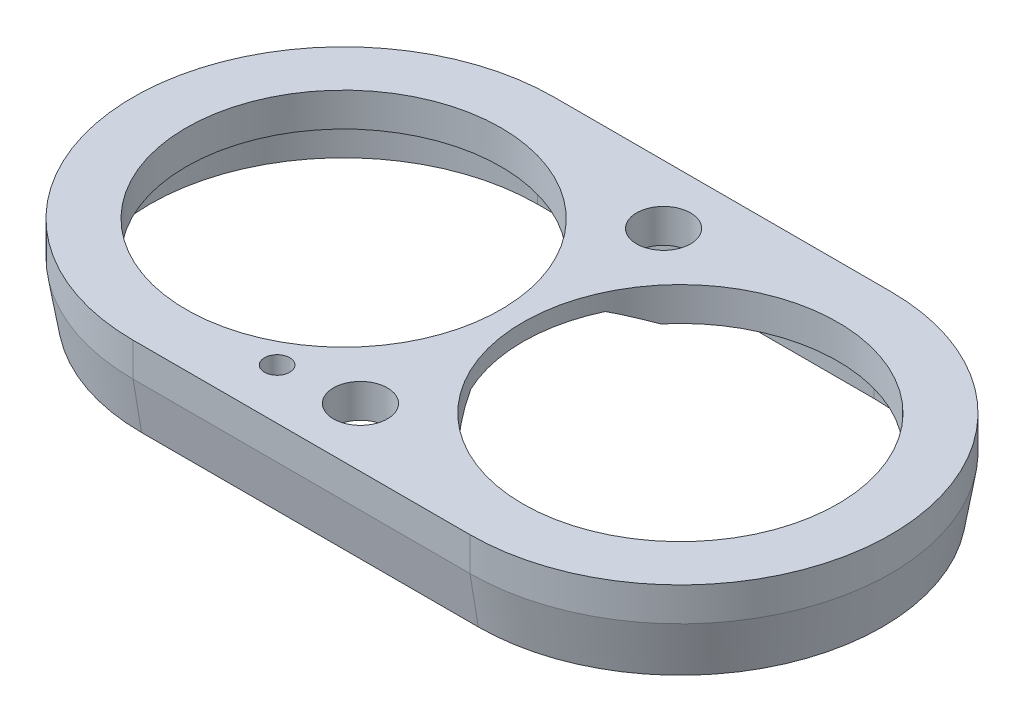
SolidWorks part; units mm, degrees
ref_plane "Front Plane" through (0, 0, 0) normal (0, 0, 1) x (1, 0, 0)
ref_plane "Top Plane" through (0, 0, 0) normal (0, 1, 0) x (1, 0, 0)
ref_plane "Right Plane" through (0, 0, 0) normal (1, 0, 0) x (0, 0, -1)
sketch "Sketch1" plane through (0, 0, 0) normal (0, 1, 0) x (1, 0, 0)
  line L2 (10, -12.5) -> (-10, -12.5)
  line L3 (0, -12.5) -> (0, 12.5)
  line L4 (-0.65, 0) -> (0.65, 0)
  line L6 (31.3696, 0) -> (-34.9839, 0) construction
  line L7 (0, -23.2241) -> (0, 19.3171) construction
  line L8 (10, 12.5) -> (-10, 12.5)
  arc A1 (10, 12.5) -> (10, -12.5) centre (10, 0) cw
  arc A2 (-10, 12.5) -> (-10, -12.5) centre (-10, 0) ccw
  point P22 (0, 0)
  dimension "D2" = 12.5
  dimension "D1" = 10
extrude "Boss-Extrude1" add sketch "Sketch1" along normal blind 2 contours A1 L8 L3 L2 | L8 A2 L2 L3 region at (10.1051, 0, 0) region at (-10.1051, 0, 0)
sketch "Sketch2" plane through (0, 2, 0) normal (0, 1, 0) x (1, 0, 0)
  line L1 (0, 16.1172) -> (0, -16.1351) construction
  circle A0 centre (10, 0) radius 9.35
  circle A1 centre (-10, 0) radius 9.35
  dimension "D2" = 18.7
  dimension "D1" = 10
extrude "Cut-Extrude1" cut sketch "Sketch2" against normal through all
sketch "Sketch3" plane through (0, 0, 0) normal (0, -1, 0) x (1, 0, 0)
  line L4 (-10, -11.5) -> (10, -11.5)
  line L5 (10, 11.5) -> (-10, 11.5)
  line L6 (-10, -11.5) -> (10, -11.5)
  line L7 (10, 11.5) -> (-10, 11.5)
  line L10 (-10, -12.5) -> (10, -12.5)
  line L11 (10, 12.5) -> (-10, 12.5)
  line L12 (-10, -12.5) -> (10, -12.5)
  line L13 (10, 12.5) -> (-10, 12.5)
  arc A4 (10, -11.5) -> (10, 11.5) centre (10, 0) ccw
  arc A5 (-10, 11.5) -> (-10, -11.5) centre (-10, 0) ccw
  arc A6 (10, -11.5) -> (10, 11.5) centre (10, 0) ccw
  arc A7 (-10, 11.5) -> (-10, -11.5) centre (-10, 0) ccw
  arc A10 (10, -12.5) -> (10, 12.5) centre (10, 0) ccw
  arc A11 (-10, 12.5) -> (-10, -12.5) centre (-10, 0) ccw
  arc A12 (10, -12.5) -> (10, 12.5) centre (10, 0) ccw
  arc A13 (-10, 12.5) -> (-10, -12.5) centre (-10, 0) ccw
  dimension "D1" = 1
  dimension "D2" = 0
extrude "Boss-Extrude3" add sketch "Sketch3" along normal blind 3
chamfer "Chamfer1" distance 3 distance2 0.5 4 edges at (22.5, -3, 0) (0, -3, -12.5) (0, -3, 12.5) (-22.5, -3, 0) first distance on face at (16.25, -0.5, 0) first distance on face at (0, -0.5, -12.5) first distance on face at (0, -0.5, 12.5) first distance on face at (-16.25, -0.5, 0)
sketch "Sketch5" plane through (0, 0, 0) normal (0, -1, 0) x (1, 0, 0)
  line L1 (-7.5, -6) -> (7.5, -6)
  line L2 (-7.5, -6) -> (-7.5, 6)
  line L3 (-7.5, 6) -> (7.5, 6)
  line L4 (7.5, -6) -> (7.5, 6)
  line L5 (-7.5, -6) -> (7.5, 6) construction
  line L6 (-7.5, 6) -> (7.5, -6) construction
  point P0 (0, 0)
  dimension "D1" = 15
  dimension "D2" = 12
extrude "Cut-Extrude3" cut sketch "Sketch5" against normal blind 1
chamfer "Chamfer2" distance 1 distance2 2 2 edges at (0, 1, -6) (0, 1, 6) first distance on face at (0, 0.5, -6) first distance on face at (0, 0.5, 6)
sketch "Sketch7" plane through (0, 2, 0) normal (0, 1, 0) x (1, 0, 0)
  line L0 (10, -12.5) -> (-10, -12.5) construction
  line L1 (10, 12.5) -> (-10, 12.5) construction
  circle A0 centre (-4.45, -9.5) radius 0.75
  circle A1 centre (0, -9) radius 1.6
  circle A2 centre (0, 9) radius 1.6
  dimension "D1" = 1.5
  dimension "D4" = 3.2
  dimension "D7" = 3.2
  dimension "D2" = 3
  dimension "D3" = 4.45
  dimension "D5" = 3.5
  dimension "D6" = 3.5
extrude "Cut-Extrude4" cut sketch "Sketch7" against normal through all
